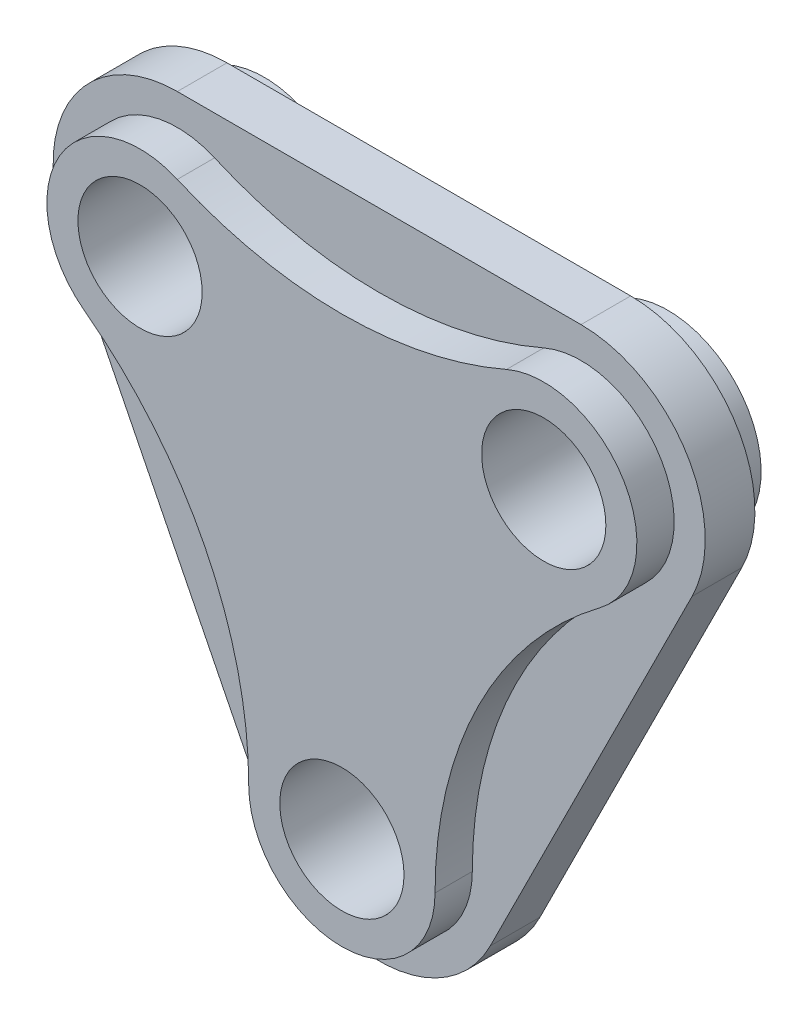
SolidWorks part; units mm, degrees
ref_plane "Front Plane" through (0, 0, 0) normal (0, 0, 1) x (1, 0, 0)
ref_plane "Top Plane" through (0, 0, 0) normal (0, 1, 0) x (1, 0, 0)
ref_plane "Right Plane" through (0, 0, 0) normal (1, 0, 0) x (0, 0, -1)
sketch "Sketch1" plane through (0, 0, 0) normal (0, 0, 1) x (1, 0, 0)
  line L0 (0, 0) -> (12973.3275, 0) construction
  line L1 (0, 0) -> (0, 12973.3275) construction
  line L2 (-50.3885, -8.9443) -> (-17.8885, -73.9443)
  line L3 (17.8885, -73.9443) -> (50.3885, -8.9443)
  line L4 (32.5, 20) -> (-32.5, 20)
  circle A0 centre (32.5, 0) radius 10
  arc A1 (41.5, -12) -> (26.5, 13.7477) centre (32.5, 0) ccw
  arc A2 (50.3885, -8.9443) -> (32.5, 20) centre (32.5, 0) ccw
  circle A3 centre (-32.5, 0) radius 10
  arc A4 (-41.5, -12) -> (-26.5, 13.7477) centre (-32.5, 0) cw
  arc A5 (-50.3885, -8.9443) -> (-32.5, 20) centre (-32.5, 0) cw
  circle A6 centre (0, -65) radius 10
  circle A7 centre (0, -65) radius 15
  arc A8 (-17.8885, -73.9443) -> (17.8885, -73.9443) centre (0, -65) ccw
  arc A9 (41.5, -12) -> (15, -65) centre (81.25, -65) ccw
  arc A10 (-41.5, -12) -> (-15, -65) centre (-81.25, -65) cw
  arc A11 (-26.5, 13.7477) -> (26.5, 13.7477) centre (0, 74.4669) ccw
  dimension "D1" = 40
  dimension "D2" = 30
  dimension "D3" = 20
  dimension "D4" = 65
  dimension "D5" = 65
extrude "Boss-Extrude1" add sketch "Sketch1" along normal mid plane 20 contours A11 A4 A10 A7 A9 A1 A3 A0 | A7 A6 region at (0, -17.0412, 0) region at (0, -79.5757, 0)
extrude "Boss-Extrude3" add sketch "Sketch1<4>" along normal mid plane 8 contours L2 A8 L3 A2 L4 A5 A4 A11 A1 A9 A7 A10 region at (-48.2499, 9.734, 0)
sketch "Sketch1<4>" plane through (0, 0, 0) normal (0, 0, 1) x (1, 0, 0) same geometry as "Sketch1"
